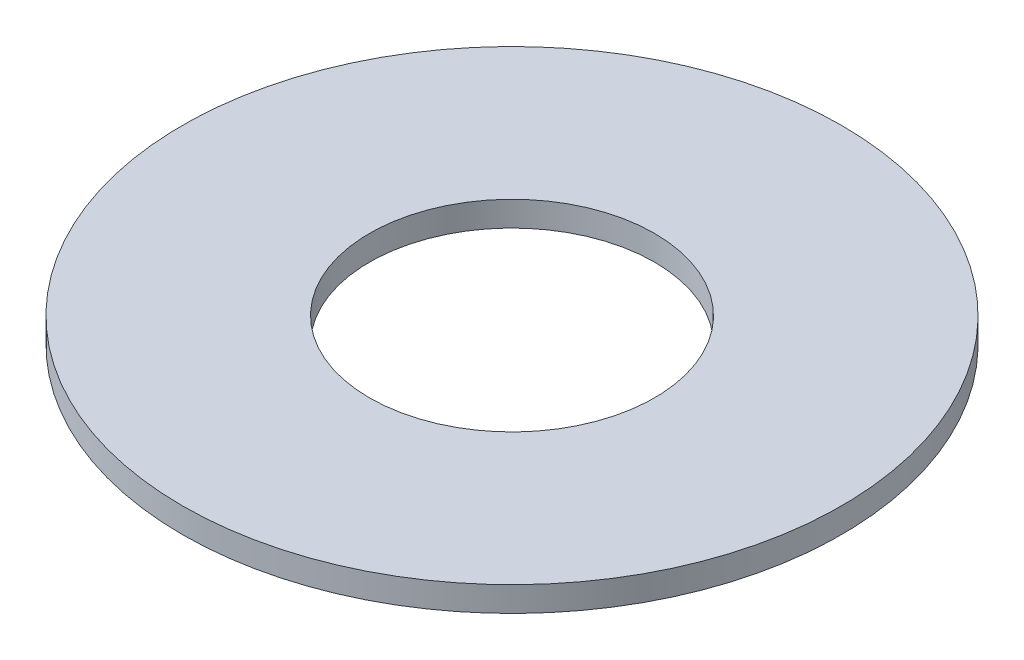
SolidWorks part; units mm, degrees
ref_plane "Front Plane" through (0, 0, 0) normal (0, 0, 1) x (1, 0, 0)
ref_plane "Top Plane" through (0, 0, 0) normal (0, 1, 0) x (1, 0, 0)
ref_plane "Right Plane" through (0, 0, 0) normal (1, 0, 0) x (0, 0, -1)
sketch "Sketch1" plane through (0, 0, 0) normal (0, 1, 0) x (1, 0, 0)
  circle A0 centre (0, 0) radius 92.5
  dimension "FLANGE_OD" = 185
extrude "Boss-Extrude1" add sketch "Sketch1" along normal blind 7
sketch "Sketch2" plane through (0, 0, 0) normal (0, 1, 0) x (1, 0, 0)
  circle A0 centre (0, 0) radius 40
  dimension "BORE_D" = 80
extrude "Cut-Extrude1" cut sketch "Sketch2" along normal through all
sketch "Sketch3" plane through (0, 7, 0) normal (0, 1, 0) x (1, 0, 0)
  circle A0 centre (0, 0) radius 26.3116 construction
  circle A1 centre (-26.3116, 0) radius 8.6658
  dimension "BOLT_D" = 17.3317
  dimension "BOLT_PCD" = 52.6233
extrude "Cut-Extrude2" cut sketch "Sketch3" against normal blind 6.8958 rebuild error yes
pattern_circular "CirPattern1" count 3 over 360 rebuild error yes
